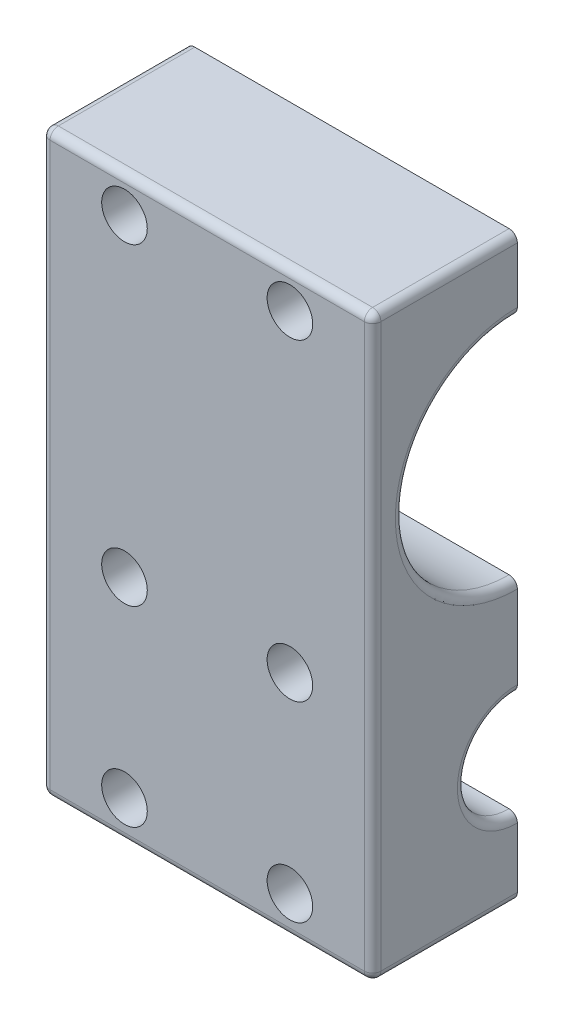
SolidWorks part; units mm, degrees
note: The reader was unsure of these and kept them because the rebuilt part matched: shared geometry of "Sketch5<3>".
ref_plane "Front Plane" through (0, 0, 0) normal (0, 0, 1) x (1, 0, 0)
ref_plane "Top Plane" through (0, 0, 0) normal (0, 1, 0) x (1, 0, 0)
ref_plane "Right Plane" through (0, 0, 0) normal (1, 0, 0) x (0, 0, -1)
sketch "Sketch1" plane through (0, 0, 0) normal (1, 0, 0) x (0, 0, -1)
  line L1 (0, 0) -> (44.45, 0)
  line L2 (0, 0) -> (0, 88.9)
  line L3 (0, 88.9) -> (44.45, 88.9)
  line L4 (44.45, 0) -> (44.45, 88.9)
  circle A0 centre (22.225, 19.685) radius 7.9375
  circle A1 centre (22.225, 60.325) radius 17.4625
  point P11 (22.225, 88.9)
  dimension "D1" = 15.875
  dimension "D2" = 34.925
  dimension "D5" = 40.64
  dimension "D3" = 44.45
  dimension "D4" = 88.9
  dimension "D6" = 28.575
extrude "Boss-Extrude1" add sketch "Sketch1" along normal blind 50.8 contours A1 | A0 | L4 L3 L2 L1
sketch "Sketch5" plane through (0, 0, 0) normal (0, 0, 1) x (1, 0, 0)
  circle A0 centre (38.1, 35.2425) radius 2.032
  circle A1 centre (38.1, 35.2425) radius 3.5
  circle A2 centre (12.7, 83.3438) radius 2.032
  circle A3 centre (12.7, 83.3438) radius 3.5
  circle A4 centre (38.1, 83.3438) radius 2.032
  circle A5 centre (38.1, 83.3438) radius 3.5
  circle A6 centre (12.7, 35.2425) radius 2.032
  circle A7 centre (12.7, 35.2425) radius 3.5
  circle A8 centre (38.1, 5.8737) radius 2.032
  circle A9 centre (38.1, 5.8737) radius 3.5
  circle A10 centre (12.7, 5.8737) radius 2.032
  circle A11 centre (12.7, 5.8737) radius 3.5
  dimension "D3" = 4.064
  dimension "D4" = 4.064
  dimension "D5" = 4.064
  dimension "D6" = 4.064
  dimension "D7" = 4.064
  dimension "D8" = 4.064
  dimension "D1" = 25.4
  dimension "D2" = 12.7
extrude "Cut-Extrude1" cut sketch "Sketch5" against normal through all contours A2 | A6 | A4 | A0 | A10 | A8
extrude "Cut-Extrude2" cut sketch "Sketch5<3>" against normal blind 15.1765 contours A3 | A5 | A1 | A7 | A11 | A9
sketch "Sketch5<3>" plane through (0, 0, 0) normal (0, 0, 1) x (1, 0, 0) same geometry as "Sketch5"
sketch "Sketch6" plane through (0, 0, -44.45) normal (0, 0, -1) x (-1, 0, 0)
  line L1 (-8.636, 83.3438) -> (-10.668, 86.8633)
  line L2 (-10.668, 86.8633) -> (-14.732, 86.8633)
  line L3 (-14.732, 86.8633) -> (-16.764, 83.3438)
  line L4 (-16.764, 83.3438) -> (-14.732, 79.8242)
  line L5 (-14.732, 79.8242) -> (-10.668, 79.8242)
  line L6 (-10.668, 79.8242) -> (-8.636, 83.3438)
  line L7 (-34.036, 83.3438) -> (-36.068, 86.8633)
  line L8 (-36.068, 86.8633) -> (-40.132, 86.8633)
  line L9 (-40.132, 86.8633) -> (-42.164, 83.3438)
  line L10 (-42.164, 83.3438) -> (-40.132, 79.8242)
  line L11 (-40.132, 79.8242) -> (-36.068, 79.8242)
  line L24 (-36.068, 79.8242) -> (-34.036, 83.3438)
  line L25 (-34.036, 35.2425) -> (-36.068, 38.762)
  line L26 (-36.068, 38.762) -> (-40.132, 38.762)
  line L39 (-40.132, 38.762) -> (-42.164, 35.2425)
  line L40 (-42.164, 35.2425) -> (-40.132, 31.723)
  line L41 (-40.132, 31.723) -> (-36.068, 31.723)
  line L54 (-36.068, 31.723) -> (-34.036, 35.2425)
  line L55 (-8.636, 35.2425) -> (-10.668, 38.762)
  line L56 (-10.668, 38.762) -> (-14.732, 38.762)
  line L69 (-14.732, 38.762) -> (-16.764, 35.2425)
  line L70 (-16.764, 35.2425) -> (-14.732, 31.723)
  line L71 (-14.732, 31.723) -> (-10.668, 31.723)
  line L84 (-10.668, 31.723) -> (-8.636, 35.2425)
  line L85 (-8.636, 5.8737) -> (-10.668, 9.3933)
  line L86 (-10.668, 9.3933) -> (-14.732, 9.3933)
  line L99 (-14.732, 9.3933) -> (-16.764, 5.8737)
  line L100 (-16.764, 5.8737) -> (-14.732, 2.3542)
  line L101 (-14.732, 2.3542) -> (-10.668, 2.3542)
  line L102 (-10.668, 2.3542) -> (-8.636, 5.8737)
  line L103 (-34.036, 5.8737) -> (-36.068, 9.3933)
  line L104 (-36.068, 9.3933) -> (-40.132, 9.3933)
  line L105 (-40.132, 9.3933) -> (-42.164, 5.8737)
  line L106 (-42.164, 5.8737) -> (-40.132, 2.3542)
  line L107 (-40.132, 2.3542) -> (-36.068, 2.3542)
  line L108 (-36.068, 2.3542) -> (-34.036, 5.8737)
  circle A7 centre (-12.7, 83.3438) radius 3.5195 construction
  circle A8 centre (-38.1, 83.3438) radius 3.5195 construction
  circle A9 centre (-38.1, 35.2425) radius 3.5195 construction
  circle A10 centre (-12.7, 35.2425) radius 3.5195 construction
  circle A11 centre (-12.7, 5.8737) radius 3.5195 construction
  circle A12 centre (-38.1, 5.8737) radius 3.5195 construction
  circle M1 centre (-12.7, 5.8737) radius 2.032
  circle M2 centre (-38.1, 35.2425) radius 2.032
  circle M3 centre (-38.1, 83.3438) radius 2.032
  circle M4 centre (-12.7, 35.2425) radius 2.032
  circle M5 centre (-38.1, 5.8737) radius 2.032
  dimension "D1" = 4.064
  dimension "D2" = 4.064
  dimension "D3" = 4.064
  dimension "D4" = 4.064
  dimension "D5" = 4.064
  dimension "D6" = 4.064
extrude "Cut-Extrude3" cut sketch "Sketch6" against normal blind 2.54 contours L11 L24 L7 L8 L9 L10 M3 | L41 L54 L25 L26 L39 L40 M2 | L71 L84 L55 L56 L69 L70 M4 | L107 L108 L103 L104 L105 L106 M5 | L101 L102 L85 L86 L99 L100 M1
fillet "Fillet1" radius 1.27 16 edges at (25.4, 0, 0) (25.4, 0, -44.45) (0, 19.685, -30.1625) (0, 0, -22.225) (50.8, 19.685, -30.1625) (50.8, 0, -22.225) (50.8, 60.325, -39.6875) (50.8, 44.45, 0) (50.8, 44.45, -44.45) (0, 60.325, -39.6875) (0, 44.45, 0) (0, 44.45, -44.45) (25.4, 88.9, 0) (0, 88.9, -22.225) (50.8, 88.9, -22.225) (25.4, 88.9, -44.45)
ref_plane "Plane1" through (0, 0, -22.225) normal (0, 0, 1) x (1, 0, 0)
other "SurfaceCut1"
